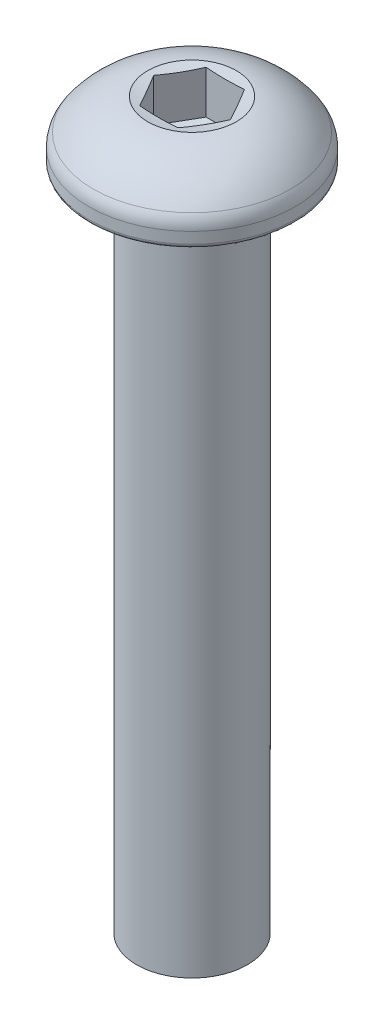
SolidWorks part; units mm, degrees
material "304 STAINLESS STEEL"
ref_plane "Front Plane" through (0, 0, 0) normal (0, 0, 1) x (1, 0, 0)
ref_plane "Top Plane" through (0, 0, 0) normal (0, 1, 0) x (1, 0, 0)
ref_plane "Right Plane" through (0, 0, 0) normal (1, 0, 0) x (0, 0, -1)
ref_axis "X-Axis" through (-88.99, 0, 0) along (1, 0, 0)
ref_axis "Y-Axis" through (0, 55, 0) along (0, -1, 0)
ref_axis "Z-Axis" through (0, 0, -88.99) along (0, 0, 1)
sketch "Sketch1" plane through (0, 0, 0) normal (0, 0, 1) x (1, 0, 0)
  line L0 (0, 0) -> (4.65, 0)
  line L1 (4.65, 0) -> (4.65, 1)
  line L2 (0, 0) -> (0, 2.7)
  line L3 (0, 2.7) -> (2, 2.7)
  arc A0 (2, 2.7) -> (4.65, 1) centre (1.6371, -0.7811) cw
  dimension "D5" = 3.5
  dimension "D1" = 4.65
  dimension "D2" = 2.7
  dimension "D3" = 2
  dimension "D4" = 1
revolve "Revolve1" add sketch "Sketch1" angle 360 about axis through (0, 55, 0) along (0, -1, 0)
fillet "Fillet1" radius 0.2 1 edges at (0, 0, 4.65)
fillet "Fillet2" radius 1 1 edges at (0, 1, 4.65)
sketch "Sketch2" plane through (0, 0, 0) normal (0, -1, 0) x (1, 0, 0)
  circle A0 centre (0, 0) radius 2.5
  dimension "D1" = 5
extrude "Boss-Extrude1" add sketch "Sketch2" along normal blind 30
sketch "Sketch6" plane through (0, 0, 0) normal (0, 0, 1) x (1, 0, 0)
  line L0 (0, 0) -> (0, 2.7)
  line L1 (2, 2.7) -> (-2, 2.7) construction
  line L2 (0, 2.7) -> (1.2742, 2.7)
  line L3 (0, 0) -> (4.45, 0)
  line L4 (4.45, 0) -> (1.2742, 2.7)
  arc A0 (4.4552, 1.2946) -> (2, 2.7) centre (1.6371, -0.7811) ccw construction
revolve "Revolve2" add sketch "Sketch6" angle 360 about axis through (0, 55, 0) along (0, -1, 0)
sketch "Sketch7" plane through (0, 2.7, 0) normal (0, 1, 0) x (1, 0, 0)
  line L1 (0.866, -1.5) -> (1.7321, 0)
  line L2 (1.7321, 0) -> (0.866, 1.5)
  line L3 (0.866, 1.5) -> (-0.866, 1.5)
  line L4 (-0.866, 1.5) -> (-1.7321, 0)
  line L5 (-1.7321, 0) -> (-0.866, -1.5)
  line L6 (-0.866, -1.5) -> (0.866, -1.5)
  circle A0 centre (0, 0) radius 1.5 construction
  dimension "D1" = 3
extrude "Cut-Extrude1" cut sketch "Sketch7" against normal blind 2
sketch "Sketch8" plane through (0, 0, 0) normal (0, 0, 1) x (1, 0, 0)
  line L0 (0, 0.7) -> (0, 0.2)
  line L1 (0, 0.7) -> (1.7321, 0.7)
  line L2 (0.866, 0.7) -> (-0.866, 0.7) construction
  line L3 (0.866, 0.7) -> (-0.866, 0.7) construction
  line L4 (-1.7321, 0.7) -> (-1.7321, 2.7) construction
  line L5 (-1.7321, 0.7) -> (-1.7321, 2.7) construction
  line L6 (1.7321, 0.7) -> (1.7321, 2.7) construction
  line L7 (1.7321, 0.7) -> (1.7321, 2.7) construction
  arc A0 (1.7321, 0.7) -> (0, 0.2) centre (-1.8962, 10.0186) cw
  dimension "D2" = 10
  dimension "D1" = 0.5
revolve "Cut-Revolve1" cut sketch "Sketch8" angle 360 about axis through (0, 55, 0) along (0, -1, 0)
sketch "Sketch9" plane through (0, 0, 0) normal (0, 0, 1) x (1, 0, 0)
  line L0 (2, 2.7) -> (-2, 2.7) construction
  line L1 (2, 2.7) -> (-2, 2.7)
  line L2 (0, 2.7) -> (0, 2.498)
  line L3 (0, 2.498) -> (-2, 2.498) construction
  arc A0 (2, 2.7) -> (0, 2.498) centre (0, 12.498) cw
  dimension "D1" = 10
revolve "Cut-Revolve2" cut sketch "Sketch9" angle 360 about axis through (0, 55, 0) along (0, -1, 0) region at (0.751, 2.6191, 0)
